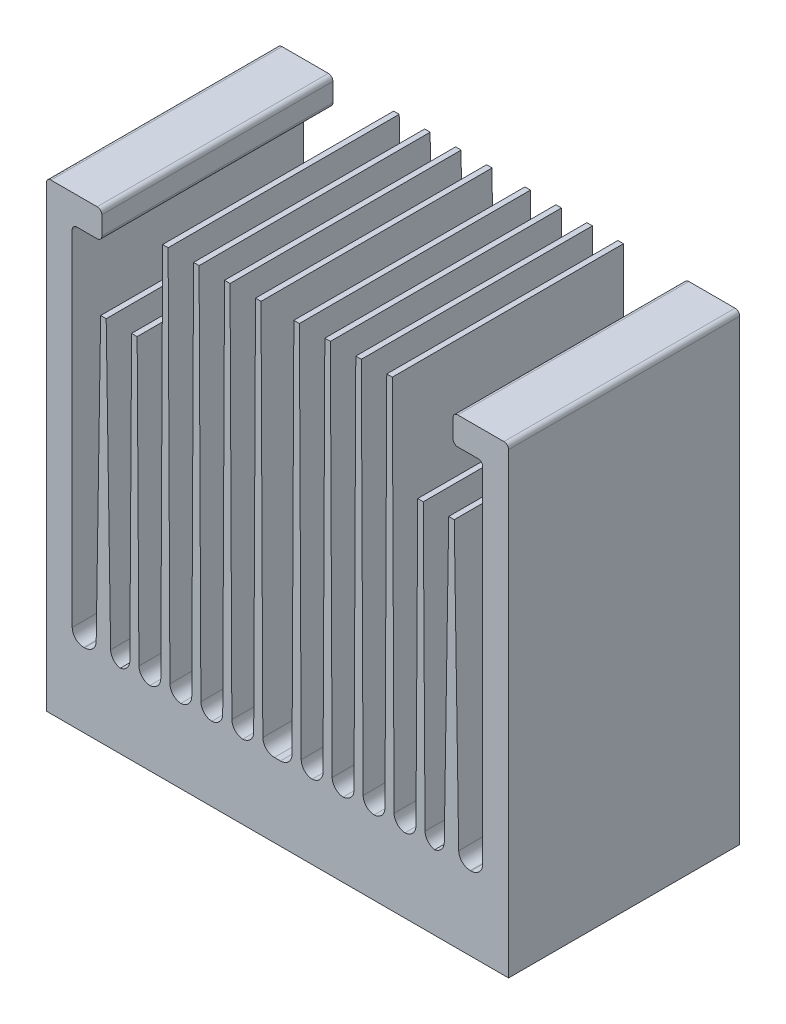
SolidWorks part; units mm, degrees
ref_plane "前视基准面" through (0, 0, 0) normal (0, 0, 1) x (1, 0, 0)
ref_plane "上视基准面" through (0, 0, 0) normal (0, 1, 0) x (1, 0, 0)
ref_plane "右视基准面" through (0, 0, 0) normal (1, 0, 0) x (0, 0, -1)
sketch "草图1" plane through (0, 0, 0) normal (0, 1, 0) x (1, 0, 0)
  line L0 (-38.2837, 0) -> (40.4297, 0) construction
  line L1 (-25, 12.5) -> (25, 12.5)
  line L2 (-25, 12.5) -> (-25, -12.5)
  line L3 (-25, -12.5) -> (25, -12.5)
  line L4 (25, 12.5) -> (25, -12.5)
  line L5 (0, 27.2258) -> (0, -28.9127) construction
  dimension "D1" = 50
  dimension "D2" = 25
extrude "拉伸1" add sketch "草图1" along normal blind 50
sketch "草图3" plane through (0, 0, -12.5) normal (0, 0, -1) x (-1, 0, 0)
  line L0 (-31.421, 8) -> (28.6536, 8) construction
  line L1 (0, -4.8742) -> (0, 56.8163) construction
  line L2 (-25, 0) -> (25, 0) construction
  line L3 (-19, 50) -> (-19, 47)
  line L4 (-19.625, 8) -> (-19.125, 40)
  line L5 (-25, 50) -> (25, 50) construction
  line L6 (-19, 47) -> (-22.2, 47)
  line L7 (-22.2, 47) -> (-22.2, 8)
  line L8 (-22.2, 8) -> (-19.625, 8)
  line L9 (-18.825, 44.483) -> (-18.825, 4.1747) construction
  line L10 (-19.125, 40) -> (-18.525, 40)
  line L11 (-18.525, 40) -> (-18.025, 8)
  line L12 (-25, 50) -> (-25, 0) construction
  line L13 (-18.025, 8) -> (-15.975, 8)
  line L14 (-15.975, 8) -> (-15.775, 40)
  line L15 (-9.275, 8) -> (-9.075, 50)
  line L16 (-15.475, 44.483) -> (-15.475, 4.9346) construction
  line L17 (-15.775, 40) -> (-15.175, 40)
  line L18 (-15.175, 40) -> (-14.975, 8)
  line L19 (-14.975, 8) -> (-12.625, 8)
  line L20 (-12.625, 8) -> (-12.425, 50)
  line L21 (-12.425, 50) -> (-11.825, 50)
  line L22 (-11.825, 50) -> (-11.625, 8)
  line L23 (-12.125, 4.9346) -> (-12.125, 53.9347) construction
  line L24 (-9.075, 50) -> (-8.475, 50)
  line L25 (-8.475, 50) -> (-8.275, 8)
  line L26 (-11.625, 8) -> (-9.275, 8)
  line L27 (-5.925, 8) -> (-5.725, 50)
  line L28 (-5.725, 50) -> (-5.125, 50)
  line L29 (-5.125, 50) -> (-4.925, 8)
  line L30 (-8.275, 8) -> (-5.925, 8)
  line L31 (-2.575, 8) -> (-2.375, 50)
  line L32 (-2.375, 50) -> (-1.775, 50)
  line L33 (-1.775, 50) -> (-1.575, 8)
  line L34 (-4.925, 8) -> (-2.575, 8)
  line L35 (-1.575, 8) -> (1.575, 8)
  line L36 (-19, 55.3463) -> (19, 55.3463)
  line L37 (12.125, 4.9346) -> (12.125, 53.9347) construction
  line L38 (15.475, 44.483) -> (15.475, 4.9346) construction
  line L39 (19, 50) -> (19, 55.3463)
  line L40 (4.925, 8) -> (2.575, 8)
  line L41 (1.775, 50) -> (1.575, 8)
  line L42 (2.375, 50) -> (1.775, 50)
  line L43 (2.575, 8) -> (2.375, 50)
  line L44 (8.275, 8) -> (5.925, 8)
  line L45 (5.125, 50) -> (4.925, 8)
  line L46 (5.725, 50) -> (5.125, 50)
  line L47 (5.925, 8) -> (5.725, 50)
  line L48 (11.625, 8) -> (9.275, 8)
  line L49 (8.475, 50) -> (8.275, 8)
  line L50 (9.075, 50) -> (8.475, 50)
  line L51 (11.825, 50) -> (11.625, 8)
  line L52 (12.425, 50) -> (11.825, 50)
  line L53 (12.625, 8) -> (12.425, 50)
  line L54 (14.975, 8) -> (12.625, 8)
  line L55 (15.175, 40) -> (14.975, 8)
  line L56 (15.775, 40) -> (15.175, 40)
  line L57 (9.275, 8) -> (9.075, 50)
  line L58 (15.975, 8) -> (15.775, 40)
  line L59 (18.025, 8) -> (15.975, 8)
  line L60 (18.525, 40) -> (18.025, 8)
  line L61 (19.125, 40) -> (18.525, 40)
  line L62 (22.2, 8) -> (19.625, 8)
  line L63 (22.2, 47) -> (22.2, 8)
  line L64 (19, 47) -> (22.2, 47)
  line L65 (-19, 50) -> (-19, 55.3463)
  line L66 (19.625, 8) -> (19.125, 40)
  line L67 (19, 50) -> (19, 47)
  point P53 (0, 55.3463)
  point P54 (0, 8)
  dimension "D1" = 8
  dimension "D2" = 6
  dimension "D3" = 3
  dimension "D4" = 0.6
  dimension "D5" = 1.6
  dimension "D6" = 2.575
  dimension "D7" = 2.8
  dimension "D8" = 40
  dimension "D9" = 0.6
  dimension "D10" = 3.35
  dimension "D11" = 1
  dimension "D12" = 3.35
  dimension "D13" = 0.6
  dimension "D14" = 1
  dimension "D15" = 4
extrude "切除-拉伸3" cut sketch "草图3" against normal through all
fillet "圆角1" radius 1.25 26 edges at (9.275, 8, 0) (5.925, 8, 0) (2.575, 8, 0) (-1.575, 8, 0) (-4.925, 8, 0) (-8.275, 8, 0) (-11.625, 8, 0) (-14.975, 8, 0) (-18.025, 8, 0) (-22.2, 8, 0) (-19.625, 8, 0) (-15.975, 8, 0) (-12.625, 8, 0) (-9.275, 8, 0) (-5.925, 8, 0) (-2.575, 8, 0) (1.575, 8, 0) (4.925, 8, 0) (8.275, 8, 0) (11.625, 8, 0) (12.625, 8, 0) (14.975, 8, 0) (15.975, 8, 0) (18.025, 8, 0) (19.625, 8, 0) (22.2, 8, 0)
fillet "圆角2" radius 0.5 8 edges at (-19, 50, 0) (-19, 47, 0) (-22.2, 47, 0) (-25, 50, 0) (19, 47, 0) (22.2, 47, 0) (19, 50, 0) (25, 50, 0)
